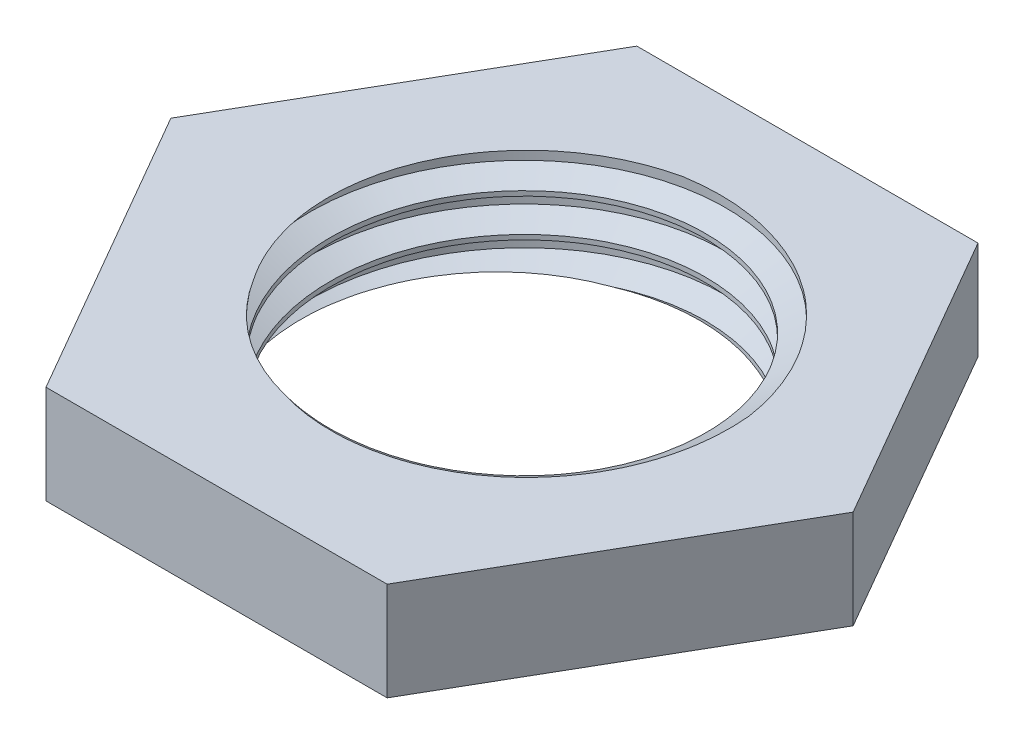
SolidWorks part; units mm, degrees
ref_plane "Front" through (0, 0, 0) normal (0, 0, 1) x (1, 0, 0)
ref_plane "Top" through (0, 0, 0) normal (0, 1, 0) x (1, 0, 0)
ref_plane "Right" through (0, 0, 0) normal (1, 0, 0) x (0, 0, -1)
sketch "Sketch1" plane through (0, 0, 0) normal (0, 1, 0) x (1, 0, 0)
  line L1 (4.5033, 0) -> (2.2517, 3.9)
  line L2 (2.2517, 3.9) -> (-2.2517, 3.9)
  line L3 (-2.2517, 3.9) -> (-4.5033, 0)
  line L4 (-4.5033, 0) -> (-2.2517, -3.9)
  line L5 (-2.2517, -3.9) -> (2.2517, -3.9)
  line L6 (2.2517, -3.9) -> (4.5033, 0)
  circle A0 centre (0, 0) radius 3.9 construction
  circle A1 centre (0, 0) radius 2.4795
  dimension "D2" = 4.959
  dimension "D1" = 7.8
extrude "Boss-Extrude1" add sketch "Sketch1" along normal blind 1.3
ref_plane "Plane1" through (0, -1, 0) normal (0, 1, 0) x (1, 0, 0)
sketch "Sketch4" plane through (0, -1, 0) normal (0, 1, 0) x (1, 0, 0)
  circle A0 centre (0, 0) radius 2.75
  dimension "D1" = 5.5
curve "Helix/Spiral2" pitch 0.5 height 2.875 radius 2.75 left hand yes centre (0, -1, 0) axis (0, 1, 0) start towards (0, 0, 1)
sketch "Sketch5" plane through (0, 0, 0) normal (1, 0, 0) x (0, 0, -1)
  line L0 (-2.75, -3) -> (-2.75, 0.2271) construction
  line L1 (-2.75, -1) -> (-3.2711, -1) construction
  line L2 (-2.75, -1) -> (-2.9851, -1) construction
  line L3 (-2.75, -1) -> (-2.75, -0.8462) construction
  line L4 (-2.2289, -1.2187) -> (-2.4794, -1.2187)
  line L5 (-2.75, -1.0625) -> (-2.4794, -1.2187)
  line L6 (-3.0206, -0.2477) -> (-3.0206, -2.1927) construction
  line L9 (-2.75, -0.9375) -> (-2.75, -1.0625)
  line L10 (-2.75, -0.9375) -> (-2.4794, -0.7813)
  line L11 (-2.4794, -0.7813) -> (-2.2289, -0.7813)
  line L15 (-2.2289, -0.7813) -> (-2.2289, -1.2187)
  point P14 (-2.75, -0.9375)
  point P16 (-2.75, -1.0625)
  dimension "D3" = 0.125
sweep "Cut-Sweep2" cut profiles "Sketch5" path "Helix/Spiral2" align with end faces yes
